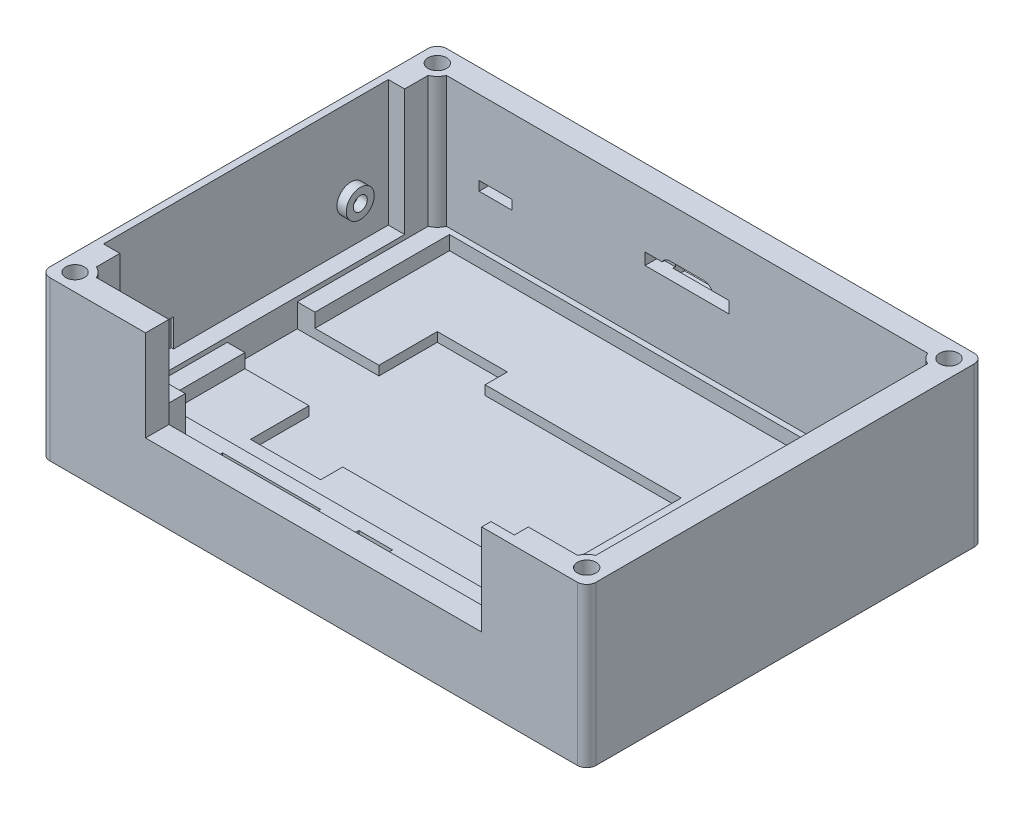
SolidWorks part; units mm, degrees
ref_plane "Front Plane" through (0, 0, 0) normal (0, 0, 1) x (1, 0, 0)
ref_plane "Top Plane" through (0, 0, 0) normal (0, 1, 0) x (1, 0, 0)
ref_plane "Right Plane" through (0, 0, 0) normal (1, 0, 0) x (0, 0, -1)
sketch "Sketch1" plane through (0, 0, 0) normal (0, 1, 0) x (1, 0, 0)
  line L1 (-58.5, 42.5) -> (58.5, 42.5)
  line L2 (-58.5, 42.5) -> (-58.5, -42.5)
  line L3 (-58.5, -42.5) -> (58.5, -42.5)
  line L4 (58.5, 42.5) -> (58.5, -42.5)
  dimension "D1" = 117
  dimension "D2" = 85
  dimension "D3" = 42.5
  dimension "D4" = 58.5
extrude "Boss-Extrude1" add sketch "Sketch1" along normal blind 34
sketch "Sketch2" plane through (0, 34, 0) normal (0, 1, 0) x (1, 0, 0)
  line L0 (-58.5, 42.5) -> (-58.5, -42.5) construction
  line L1 (-53.5, 37.5) -> (53.5, 37.5)
  line L2 (-53.5, 37.5) -> (-53.5, -37.5)
  line L3 (-53.5, -37.5) -> (53.5, -37.5)
  line L4 (53.5, 37.5) -> (53.5, -37.5)
  line L5 (58.5, -42.5) -> (58.5, 42.5) construction
  line L6 (58.5, 42.5) -> (-58.5, 42.5) construction
  line L7 (-58.5, -42.5) -> (58.5, -42.5) construction
  dimension "D1" = 5
  dimension "D2" = 5
  dimension "D3" = 5
  dimension "D4" = 5
extrude "Cut-Extrude1" cut sketch "Sketch2" against normal blind 28
sketch "Sketch3" plane through (0, 6, 0) normal (0, 1, 0) x (1, 0, 0)
  line L0 (58.5, -42.5) -> (58.5, 42.5) construction
  line L1 (-58.5, -42.5) -> (58.5, -42.5) construction
  line L2 (58.5, 42.5) -> (-58.5, 42.5) construction
  line L3 (-58.5, 42.5) -> (-58.5, -42.5) construction
  circle A2 centre (54.8, -38.8) radius 2
  circle A4 centre (54.8, 38.8) radius 2
  circle A6 centre (-54.8, 38.8) radius 2
  circle A8 centre (-54.8, -38.8) radius 2
  dimension "D1" = 4
  dimension "D5" = 4
  dimension "D9" = 4
  dimension "D13" = 4
  dimension "D3" = 3.7
  dimension "D4" = 3.7
  dimension "D7" = 3.7
  dimension "D8" = 3.7
  dimension "D11" = 3.7
  dimension "D12" = 3.7
  dimension "D15" = 3.7
  dimension "D16" = 3.7
extrude "Cut-Extrude2" cut sketch "Sketch3" against normal blind 28 and the other way blind 28
sketch "Sketch6" plane through (22.6275, 6, 6.5024) normal (0, 1, 0) x (1, 0, 0)
  line L0 (-76.1275, 43.7825) -> (-76.1275, -30.7778) construction
  line L1 (-43.6275, -8.7476) -> (-1.6275, -8.7476)
  line L2 (-43.6275, -8.7476) -> (-43.6275, 21.7524)
  line L3 (-43.6275, 21.7524) -> (-1.6275, 21.7524)
  line L4 (-1.6275, -8.7476) -> (-1.6275, 21.7524)
  line L5 (-75.9076, -30.9976) -> (30.6527, -30.9976) construction
  line L6 (30.6527, 44.0024) -> (-75.9076, 44.0024) construction
  line L7 (30.8725, -30.7778) -> (30.8725, 43.7825) construction
  dimension "D1" = 42
  dimension "D2" = 30.5
  dimension "D3" = 32.5
  dimension "D4" = 22.25
  dimension "D5" = 22.25
  dimension "D6" = 30.5
  dimension "D7" = 32.5
sketch "Sketch11" plane through (0, 6, 0) normal (0, 1, 0) x (1, 0, 0)
  circle A0 centre (-54.8, -38.8) radius 3.5
  circle A1 centre (-54.8, 38.8) radius 3.5
  circle A2 centre (54.8, -38.8) radius 3.5
  circle A3 centre (54.8, 38.8) radius 3.5
  dimension "D1" = 7
  dimension "D2" = 7
  dimension "D3" = 7
  dimension "D4" = 7
extrude "Boss-Extrude3" add sketch "Sketch11" along normal blind 28
sketch "Sketch13" plane through (0, 34, 0) normal (0, 1, 0) x (1, 0, 0)
  line L0 (-58.5, -42.5) -> (58.5, -42.5) construction
  line L1 (58.5, -42.5) -> (58.5, 42.5) construction
  circle A0 centre (-54.8, 38.8) radius 2
  circle A1 centre (54.8, 38.8) radius 2
  circle A2 centre (-54.8, -38.8) radius 2
  circle A3 centre (54.8, -38.8) radius 2
  dimension "D1" = 4
  dimension "D4" = 4
  dimension "D5" = 4
  dimension "D6" = 4
  dimension "D2" = 3.7
  dimension "D3" = 3.7
extrude "Cut-Extrude9" cut sketch "Sketch13" against normal through all
sketch "Sketch14" plane through (0, 6, 0) normal (0, 1, 0) x (1, 0, 0)
  line L0 (53.5, -35.5504) -> (53.5, 35.5504) construction
  line L1 (-49.7, -25.7) -> (52.3, -25.7)
  line L2 (-49.7, -25.7) -> (-49.7, 36.3)
  line L3 (-49.7, 36.3) -> (52.3, 36.3)
  line L4 (52.3, -25.7) -> (52.3, 36.3)
  line L5 (51.5504, 37.5) -> (-51.5504, 37.5) construction
  dimension "D1" = 102
  dimension "D2" = 62
  dimension "D3" = 1.2
  dimension "D4" = 1.2
extrude "Cut-Extrude10" cut sketch "Sketch14" against normal blind 3
sketch "Sketch15" plane through (-53.5, 0, 0) normal (1, 0, 0) x (0, 0, -1)
  line L0 (-35.5504, 6) -> (-35.5504, 34) construction
  line L1 (-30.5004, 47) -> (30.4996, 47)
  line L2 (-30.5004, 47) -> (-30.5004, 7)
  line L3 (-30.5004, 7) -> (30.4996, 7)
  line L4 (30.4996, 47) -> (30.4996, 7)
  line L5 (35.5504, 34) -> (35.5504, 6) construction
  line L6 (35.5504, 6) -> (-35.5504, 6) construction
  line L7 (35.5504, 34) -> (-35.5504, 34) construction
  dimension "D1" = 61
  dimension "D2" = 40
  dimension "D3" = 5.05
  dimension "D4" = 5.0508
  dimension "D5" = 1
  dimension "D6" = 27
extrude "Cut-Extrude11" cut sketch "Sketch15" against normal blind 3.5
sketch "Sketch16" plane through (-57, 0, 0) normal (1, 0, 0) x (0, 0, -1)
  line L1 (-30.5004, 7) -> (-15.5004, 7)
  line L2 (-30.5004, 7) -> (-30.5004, 13)
  line L3 (-30.5004, 13) -> (-15.5004, 13)
  line L4 (-15.5004, 7) -> (-15.5004, 13)
  dimension "D1" = 6
  dimension "D2" = 15
extrude "Cut-Extrude12" cut sketch "Sketch16" against normal blind 0.5
sketch "Sketch18" plane through (0, 0, -42.5) normal (0, 0, -1) x (-1, 0, 0)
  line L0 (-3.725, 21.75) -> (3.725, 21.75) construction
  line L1 (-3.725, 23.5) -> (3.725, 23.5)
  line L2 (-3.725, 20) -> (3.725, 20)
  line L3 (-58.5, 34) -> (-58.5, 0) construction
  line L4 (-58.5, 0) -> (58.5, 0) construction
  arc A0 (-3.725, 23.5) -> (-3.725, 20) centre (-3.725, 21.75) ccw
  arc A1 (3.725, 20) -> (3.725, 23.5) centre (3.725, 21.75) ccw
  point P2 (0, 21.75)
  dimension "D1" = 58.5
  dimension "D2" = 7.45
  dimension "D3" = 3.5
  dimension "D4" = 21.75
extrude "Cut-Extrude13" cut sketch "Sketch18" against normal blind 5
sketch "Sketch20" plane through (0, 0, 42.5) normal (0, 0, 1) x (1, 0, 0)
  line L0 (-58.5, 34) -> (-58.5, 0) construction
  line L1 (-36, 39.5) -> (36, 39.5)
  line L2 (-36, 39.5) -> (-36, 14.5)
  line L3 (-36, 14.5) -> (36, 14.5)
  line L4 (36, 39.5) -> (36, 14.5)
  line L5 (-58.5, 0) -> (58.5, 0) construction
  line L6 (-58.5, 34) -> (58.5, 34) construction
  dimension "D1" = 72
  dimension "D2" = 25
  dimension "D3" = 22.5
  dimension "D4" = 14.5
  dimension "D5" = 19.5
extrude "Cut-Extrude14" cut sketch "Sketch20" against normal blind 5
sketch "Sketch21" plane through (0, 0, -37.5) normal (0, 0, 1) x (1, 0, 0)
  line L0 (52.3, 6) -> (-49.7, 6) construction
  line L1 (-44.5504, 18) -> (-37.5504, 18)
  line L2 (-44.5504, 18) -> (-44.5504, 16)
  line L3 (-44.5504, 16) -> (-37.5504, 16)
  line L4 (-37.5504, 18) -> (-37.5504, 16)
  line L5 (-51.5504, 6) -> (-51.5504, 34) construction
  line L7 (51.5504, 6) -> (-51.5504, 6) construction
  line L8 (37.5504, 16) -> (44.5504, 16)
  line L9 (37.5504, 16) -> (37.5504, 18)
  line L10 (37.5504, 18) -> (44.5504, 18)
  line L11 (44.5504, 16) -> (44.5504, 18)
  line L12 (51.5504, 34) -> (51.5504, 6) construction
  dimension "D1" = 10
  dimension "D2" = 2
  dimension "D3" = 7
  dimension "D4" = 7
  dimension "D5" = 7
  dimension "D6" = 2
  dimension "D7" = 10
  dimension "D8" = 7
  dimension "D9" = 75.1008
extrude "Cut-Extrude15" cut sketch "Sketch21" against normal blind 2
sketch "Sketch22" plane through (0, 0, 37.5) normal (0, 0, -1) x (-1, 0, 0)
  line L0 (51.5504, 6) -> (-51.5504, 6) construction
  line L1 (-47.3004, 16) -> (-40.3004, 16)
  line L2 (-47.3004, 16) -> (-47.3004, 14)
  line L3 (-47.3004, 14) -> (-40.3004, 14)
  line L4 (-40.3004, 16) -> (-40.3004, 14)
  line L5 (38.4904, 16) -> (45.4904, 16)
  line L6 (38.4904, 16) -> (38.4904, 14)
  line L7 (38.4904, 14) -> (45.4904, 14)
  line L8 (45.4904, 16) -> (45.4904, 14)
  line L9 (-51.5504, 6) -> (-51.5504, 34) construction
  line L11 (51.5504, 34) -> (51.5504, 6) construction
  dimension "D1" = 8
  dimension "D2" = 8
  dimension "D3" = 2
  dimension "D4" = 7
  dimension "D5" = 4.25
  dimension "D6" = 7
  dimension "D7" = 2
  dimension "D8" = 6.06
extrude "Boss-Extrude5" add sketch "Sketch22" along normal blind 2.5
sketch "Sketch23" plane through (0, 0, 37.5) normal (0, 0, -1) x (-1, 0, 0)
  line L0 (-47.3004, 14) -> (-40.3004, 14) construction
  line L1 (-45.3004, 14) -> (-42.3004, 14)
  line L2 (-45.3004, 14) -> (-45.3004, 12.5)
  line L3 (-45.3004, 12.5) -> (-42.3004, 12.5)
  line L4 (-42.3004, 14) -> (-42.3004, 12.5)
  line L5 (-51.5504, 6) -> (-51.5504, 34) construction
  line L6 (38.4904, 14) -> (45.4904, 14) construction
  line L7 (42.3004, 14) -> (45.3004, 14)
  line L8 (42.3004, 14) -> (42.3004, 12.5)
  line L9 (42.3004, 12.5) -> (45.3004, 12.5)
  line L10 (45.3004, 14) -> (45.3004, 12.5)
  line L11 (51.5504, 34) -> (51.5504, 6) construction
  point P6 (-45.3004, 13.25)
  dimension "D1" = 3
  dimension "D2" = 6.25
  dimension "D3" = 1.5
  dimension "D4" = 6.25
  dimension "D5" = 3
  dimension "D6" = 1.5
extrude "Boss-Extrude6" add sketch "Sketch23" along normal blind 2.5
sketch "Sketch25" plane through (45.3004, 0, 0) normal (1, 0, 0) x (0, 0, -1)
  line L0 (-35, 14) -> (-37.5, 12.5)
  line L1 (-37.5, 12.5) -> (-35, 12.5)
  line L2 (-35, 12.5) -> (-35, 14)
extrude "Cut-Extrude17" cut sketch "Sketch25" against normal blind 92.5
sketch "Sketch38" plane through (0, 6, 0) normal (0, 1, 0) x (1, 0, 0)
  line L0 (-53.5, 35.5504) -> (-53.5, -35.5504) construction
  line L1 (-33.5, -28.5) -> (-12.5, -28.5)
  line L2 (-33.5, -28.5) -> (-33.5, -35.5)
  line L3 (-33.5, -35.5) -> (-12.5, -35.5)
  line L4 (-12.5, -28.5) -> (-12.5, -35.5)
  line L5 (-51.5504, -37.5) -> (51.5504, -37.5) construction
  point P6 (-33.5, -32)
  dimension "D1" = 7
  dimension "D2" = 21
  dimension "D3" = 20
  dimension "D4" = 2
extrude "Cut-Extrude22" cut sketch "Sketch38" against normal blind 4
sketch "Sketch39" plane through (0, 2, 0) normal (0, 1, 0) x (1, 0, 0)
  line L0 (-33.5, -35.5) -> (-12.5, -35.5) construction
  line L1 (-27, -30) -> (-19, -30)
  line L2 (-27, -30) -> (-27, -34)
  line L3 (-27, -34) -> (-19, -34)
  line L4 (-19, -30) -> (-19, -34)
  line L6 (-33.5, -28.5) -> (-33.5, -35.5) construction
  line L7 (-12.5, -35.5) -> (-12.5, -28.5) construction
  line L8 (-33.5, -35.5) -> (-12.5, -35.5) construction
  circle A0 centre (-31, -32) radius 1.6
  circle A1 centre (-15, -32) radius 1.6
  point P14 (-12.5, -32)
  dimension "D5" = 3.2
  dimension "D6" = 3.2
  dimension "D1" = 4
  dimension "D2" = 8
  dimension "D3" = 1.5
  dimension "D4" = 6.5
  dimension "D7" = 2.5
  dimension "D8" = 2.5
  dimension "D9" = 3.5
  dimension "D10" = 3.5
extrude "Cut-Extrude23" cut sketch "Sketch39" against normal through all and the other way through all
sketch "Sketch40" plane through (0, 6, 0) normal (0, 1, 0) x (1, 0, 0)
  line L0 (-53.5, 35.5504) -> (-53.5, -35.5504) construction
  line L1 (-4.5, -28.3) -> (2.7, -28.3)
  line L2 (-4.5, -28.3) -> (-4.5, -35.5)
  line L3 (-4.5, -35.5) -> (2.7, -35.5)
  line L4 (2.7, -28.3) -> (2.7, -35.5)
  line L5 (-51.5504, -37.5) -> (51.5504, -37.5) construction
  dimension "D1" = 7.2
  dimension "D2" = 7.2
  dimension "D3" = 49
  dimension "D4" = 2
extrude "Cut-Extrude24" cut sketch "Sketch40" against normal blind 4
sketch "Sketch41" plane through (0, 2, 0) normal (0, 1, 0) x (1, 0, 0)
  line L0 (-4.5, -28.3) -> (-4.5, -35.5) construction
  line L1 (-4.5, -35.5) -> (2.7, -35.5) construction
  circle A0 centre (-0.9, -31.9) radius 2.5
  dimension "D1" = 5
  dimension "D2" = 3.6
  dimension "D3" = 3.6
extrude "Cut-Extrude25" cut sketch "Sketch41" against normal blind 4
fillet "Fillet5" radius 2 1 edges at (-58.5, 17, 42.5) type face fillet first side face at (-58.5, 17, 0) second side face at (0, 20.625, 42.5)
fillet "Fillet6" radius 2 1 edges at (58.5, 17, 42.5) type face fillet first side face at (0.5, 20.625, 42.5) second side face at (58.5, 17, 0)
fillet "Fillet7" radius 2 1 edges at (58.5, 17, -42.5) type face fillet first side face at (58.5, 17, -1) second side face at (0, 21.75, -42.5)
fillet "Fillet8" radius 2 1 edges at (-58.5, 17, -42.5) type face fillet first side face at (0, 21.75, -42.5) second side face at (-58.5, 17, -1)
extrude "Cut-Extrude26" cut sketch "Sketch6" against normal blind 5
sketch "Sketch42" plane through (0, 3, 0) normal (0, 1, 0) x (1, 0, 0)
  line L0 (-21, 15.25) -> (-21, -15.25) construction
  line L1 (-21, -20) -> (-36, -20)
  line L2 (-21, -20) -> (-21, 20)
  line L3 (-21, 20) -> (-36, 20)
  line L4 (-36, -20) -> (-36, -7.5)
  line L5 (51.5504, 37.5) -> (-51.5504, 37.5) construction
  line L6 (-51.5504, -37.5) -> (51.5504, -37.5) construction
  line L7 (-53.5, 35.5504) -> (-53.5, -35.5504) construction
  line L8 (-36, -7.5) -> (-53.5, -7.5)
  line L10 (-36, 7.5) -> (-53.5, 7.5)
  line L11 (-53.5, -7.5) -> (-53.5, 7.5)
  line L12 (-36, 7.5) -> (-36, 20)
  dimension "D1" = 40
  dimension "D2" = 17.5
  dimension "D3" = 17.5
  dimension "D4" = 15
  dimension "D5" = 12.5
  dimension "D6" = 15
  dimension "D7" = 12.5
extrude "Cut-Extrude27" cut sketch "Sketch42" against normal blind 2 and the other way blind 5
sketch "Sketch43" plane through (-57, 0, 0) normal (1, 0, 0) x (0, 0, -1)
  line L0 (-15.5004, 7) -> (30.4996, 7) construction
  line L1 (30.4996, 7) -> (30.4996, 34) construction
  circle A0 centre (22.4996, 16) radius 1.5
  circle A1 centre (22.4996, 16) radius 3
  dimension "D3" = 3
  dimension "D4" = 6
  dimension "D1" = 9
  dimension "D2" = 8
extrude "Boss-Extrude7" add sketch "Sketch43" along normal blind 2
sketch "Sketch44" plane through (0, 0, 37.5) normal (0, 0, -1) x (-1, 0, 0)
  line L0 (-36, 34) -> (-51.5504, 34) construction
  line L2 (-36, 14.5) -> (-36, 34)
  line L3 (-36, 34) -> (-41, 34)
  line L4 (-41, 18.5) -> (-41, 34)
  line L5 (-41, 18.5) -> (-36, 18.5)
  line M24 (-36, 34) -> (-51.5504, 34)
  dimension "D1" = 5
  dimension "D2" = 15.5
extrude "Cut-Extrude28" cut sketch "Sketch44" against normal blind 3 contours L4 L5 L2 M24 region at (38.5, 26.25, 37.5)
sketch "Sketch45" plane through (0, 0, -37.5) normal (0, 0, 1) x (1, 0, 0)
  line L0 (-3.725, 23.5) -> (3.725, 23.5) construction
  line L1 (-9, 20) -> (9, 20)
  line L2 (-9, 20) -> (-9, 22.5)
  line L3 (-9, 22.5) -> (9, 22.5)
  line L4 (9, 20) -> (9, 22.5)
  arc A0 (-3.725, 23.5) -> (-3.725, 20) centre (-3.725, 21.75) ccw construction
  arc A1 (3.725, 20) -> (3.725, 23.5) centre (3.725, 21.75) ccw construction
  dimension "D1" = 2.5
  dimension "D2" = 18
  dimension "D3" = 5.275
  dimension "D4" = 5.275
  dimension "D5" = 3.5
extrude "Cut-Extrude29" cut sketch "Sketch45" against normal blind 3
sketch "Sketch47" plane through (0, 0, -42.5) normal (0, 0, -1) x (-1, 0, 0)
  line L0 (-3.725, 20) -> (3.725, 20) construction
  line L1 (-5.525, 25.25) -> (5.525, 25.25)
  line L2 (-5.525, 25.25) -> (-5.525, 18.25)
  line L3 (-5.525, 18.25) -> (5.525, 18.25)
  line L4 (5.525, 25.25) -> (5.525, 18.25)
  line L5 (3.725, 23.5) -> (-3.725, 23.5) construction
  arc A0 (-3.725, 23.5) -> (-3.725, 20) centre (-3.725, 21.75) ccw construction
  arc A1 (3.725, 20) -> (3.725, 23.5) centre (3.725, 21.75) ccw construction
  dimension "D1" = 1.8
  dimension "D2" = 1.8
  dimension "D3" = 1.75
  dimension "D4" = 7
  dimension "D5" = 1.75
  dimension "D6" = 11.05
extrude "Cut-Extrude30" cut sketch "Sketch47" against normal blind 2.5
sketch "Sketch48" plane through (0, 16, 0) normal (0, 1, 0) x (1, 0, 0)
  line L0 (40.3004, -35) -> (40.3004, -37.5) construction
  line L1 (47.3004, -37.5) -> (40.3004, -37.5)
  line L2 (47.3004, -37.5) -> (47.3004, -31.5)
  line L3 (47.3004, -31.5) -> (40.3004, -31.5)
  line L4 (40.3004, -37.5) -> (40.3004, -31.5)
  dimension "D1" = 6
extrude "Boss-Extrude8" add sketch "Sketch48" against normal blind 10
sketch "Sketch49" plane through (0, 16, 0) normal (0, 1, 0) x (1, 0, 0)
  line L0 (-38.4904, -35) -> (-38.4904, -37.5) construction
  line L1 (-45.4904, -37.5) -> (-38.4904, -37.5)
  line L2 (-45.4904, -37.5) -> (-45.4904, -31.5)
  line L3 (-45.4904, -31.5) -> (-38.4904, -31.5)
  line L4 (-38.4904, -37.5) -> (-38.4904, -31.5)
  dimension "D1" = 6
extrude "Boss-Extrude9" add sketch "Sketch49" against normal blind 10
sketch "Sketch50" plane through (0, 16, 0) normal (0, 1, 0) x (1, 0, 0)
  line L0 (47.3004, -37.5) -> (47.3004, -31.5) construction
  line L1 (41, -37.5) -> (51.5504, -37.5) construction
  circle A0 centre (43.7954, -34.5) radius 1.5
  dimension "D1" = 3
  dimension "D2" = 3.505
  dimension "D3" = 3
sketch "Sketch51" plane through (0, 16, 0) normal (0, 1, 0) x (1, 0, 0)
  line L0 (-45.4904, -37.5) -> (-38.4904, -37.5) construction
  line L1 (-45.4904, -31.5) -> (-45.4904, -37.5) construction
  circle A0 centre (-41.9854, -34.5) radius 1.5
  dimension "D1" = 3
  dimension "D2" = 3
  dimension "D3" = 3.505
extrude "Cut-Extrude31" cut sketch "Sketch51" against normal blind 8
extrude "Cut-Extrude32" cut sketch "Sketch50" against normal blind 8
